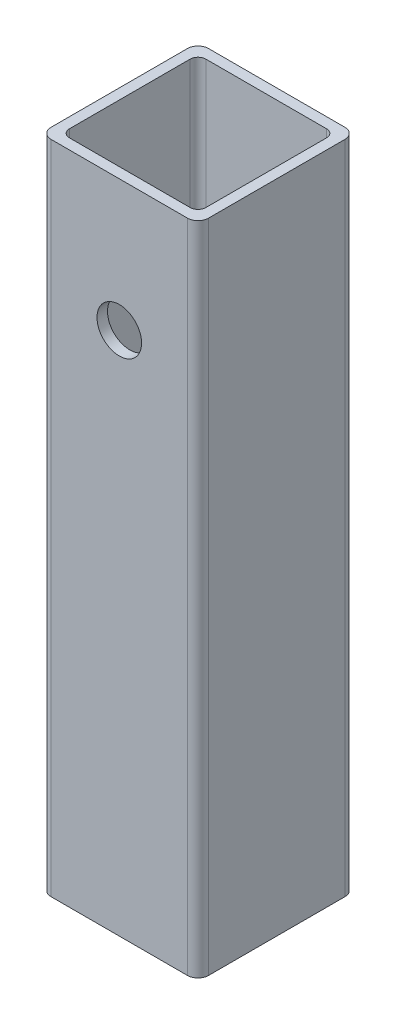
SolidWorks part; units mm, degrees
material "AISI 1020"
ref_plane "Спереди" through (0, 0, 0) normal (0, 0, 1) x (1, 0, 0)
ref_plane "Сверху" through (0, 0, 0) normal (0, 1, 0) x (1, 0, 0)
ref_plane "Справа" through (0, 0, 0) normal (1, 0, 0) x (0, 0, -1)
sketch "Эскиз1" plane through (0, 0, 0) normal (0, 1, 0) x (1, 0, 0)
  line L0 (1005, 0) -> (0, 0) construction
  line L1 (0, 1080) -> (0, 0) construction
  line B0 (-56, 0) -> (-4, 0)
  line B1 (-60, -4) -> (-60, -56)
  line B2 (-56, -60) -> (-4, -60)
  line B3 (0, -4) -> (0, -56)
  line B4 (-53, -4) -> (-7, -4)
  line B5 (-56, -7) -> (-56, -53)
  line B6 (-53, -56) -> (-7, -56)
  line B7 (-4, -7) -> (-4, -53)
  arc B8 (-60, -56) -> (-56, -60) centre (-56, -56) ccw
  arc B9 (-4, -60) -> (0, -56) centre (-4, -56) ccw
  arc B10 (-4, 0) -> (0, -4) centre (-4, -4) cw
  arc B11 (-56, 0) -> (-60, -4) centre (-56, -4) ccw
  arc B12 (-56, -53) -> (-53, -56) centre (-53, -53) ccw
  arc B13 (-7, -56) -> (-4, -53) centre (-7, -53) ccw
  arc B14 (-7, -4) -> (-4, -7) centre (-7, -7) cw
  arc B15 (-53, -4) -> (-56, -7) centre (-53, -7) ccw
sketch_block_instance "60х60х4-1"
sketch_block "60х60х4" parameters "D3"=4, "D4"=3, "D1"=60, "D2"=4
extrude "Бобышка-Вытянуть1" add sketch "Эскиз1" along normal blind 100 and the other way blind 150
sketch "Эскиз2" plane through (0, 0, 60) normal (0, 0, 1) x (1, 0, 0)
  line L0 (-30, -150) -> (-30, 2719.7263) construction
  line L1 (-56, 100) -> (-4, 100) construction
  circle A0 centre (-30, 50) radius 8.5
  dimension "D1" = 17
  dimension "D2" = 50
extrude "Вырез-Вытянуть1" cut sketch "Эскиз2" against normal through all
